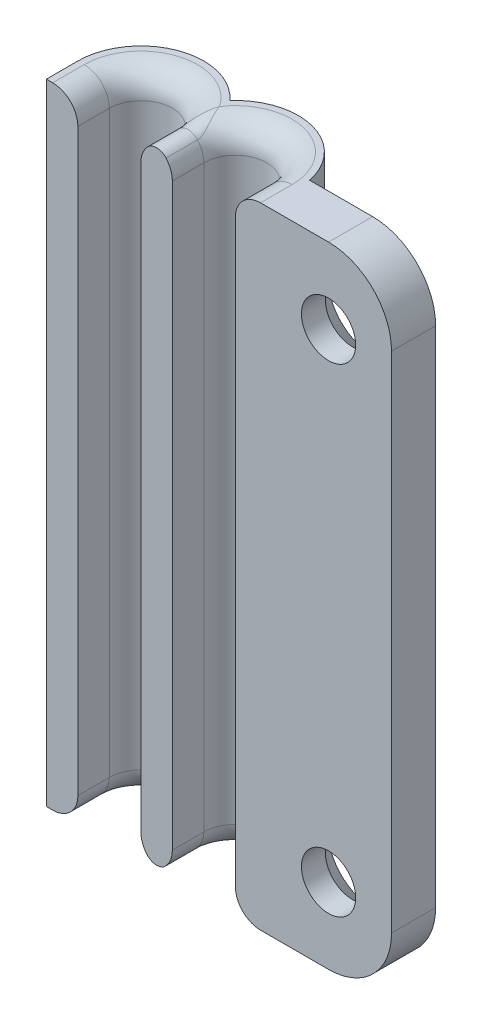
SolidWorks part; units mm, degrees
ref_plane "Top" through (0, 0, 0) normal (0, 0, 1) x (1, 0, 0)
ref_plane "Front" through (0, 0, 0) normal (0, 1, 0) x (1, 0, 0)
ref_plane "Right" through (0, 0, 0) normal (1, 0, 0) x (0, 0, -1)
sketch "Profile Sketch" plane through (0, 0, 0) normal (0, 1, 0) x (1, 0, 0)
  line L1 (0, 0) -> (0, 3.5)
  line L5 (-27.399, 2.5) -> (-27.399, 0)
  line L6 (-19.899, 2.5) -> (-19.899, 0)
  line L7 (-24.899, 2.5) -> (-24.899, 0)
  line L8 (-17.399, 2.5) -> (-17.399, 0)
  line L9 (-12.399, 2.5) -> (-12.399, 0)
  line L10 (-12.399, 0) -> (0, 0)
  line L11 (0, 3.5) -> (-10, 3.5)
  line L13 (-19.899, 0) -> (-17.399, 0)
  line L14 (-24.899, 0) -> (-27.399, 0)
  line L15 (-22.399, 5) -> (-14.899, 5) construction
  arc A0 (-19.899, 2.5) -> (-24.899, 2.5) centre (-22.399, 2.5) ccw
  arc A1 (-12.399, 2.5) -> (-17.399, 2.5) centre (-14.899, 2.5) ccw
  arc A2 (-18.649, 5.8072) -> (-27.399, 2.5) centre (-22.399, 2.5) ccw
  arc A3 (-10, 3.5) -> (-18.649, 5.8072) centre (-14.899, 2.5) ccw
  point P20 (0, 0)
  point P21 (-15, 8.8173)
  point P22 (0, 0)
  dimension "D1" = 3.5
  dimension "D2" = 2.5
  dimension "D4" = 2.5
  dimension "D3" = 10
  dimension "D5" = 5
extrude "Profile Extrude" add sketch "Profile Sketch" along normal blind 50
fillet "Corner Fillets" radius 5 2 edges at (0, 50, -1.75) (0, 0, -1.75)
fillet "Entrance Fillets" radius 2 12 edges at (-22.399, 0, -5) (-14.899, 0, -5) (-14.899, 50, -5) (-22.399, 50, -5) (-24.899, 0, -1.25) (-19.899, 0, -1.25) (-17.399, 0, -1.25) (-12.399, 0, -1.25) (-17.399, 50, -1.25) (-12.399, 50, -1.25) (-24.899, 50, -1.25) (-19.899, 50, -1.25)
fillet "Center Fillets" radius 1 4 edges at (-18.649, 0.146, -1.25) (-18.649, 49.854, -1.25)
hole_wizard "No. 6 Mounting Screws" positions "No. 6 Mounting Screws Position Sketch" profile "No. 6 Mounting Screws Profile Sketch" countersink size "#6" standard "ANSI Inch" end condition through all
sketch "No. 6 Mounting Screws Position Sketch" plane through (0, 0, -3.5) normal (0, 0, -1) x (-1, 0, 0)
  line L0 (0, 25) -> (10, 25) construction
  line L4 (5, 25) -> (5, 0) construction
  line L8 (0, 45) -> (0, 5) construction
  line L10 (5, 0) -> (10, 0) construction
  line L11 (5, 50) -> (10, 50) construction
  line L12 (10, 50) -> (10, 0) construction
  point P0 (5, 44)
  point P2 (5, 6)
  point P24 (0, 0)
  point P25 (0, 0)
  point P26 (9.2002, 20.8342)
  point P27 (0, 0)
  point P28 (1.6699, 20.8753)
  point P31 (0, 0)
  point P34 (0, 0)
  point P35 (0, 0)
  point P38 (5, 9.2061)
  point P41 (0, 0)
  point P42 (0, 0)
  point P43 (0, 0)
  point P44 (0, 0)
  point P45 (0, 0)
  point P46 (0, 0)
  point P47 (7.4558, 23.612)
  point P48 (0, 0)
sketch "No. 6 Mounting Screws Profile Sketch" plane through (-5, 44, -3.5) normal (1, 0, 0) x (0, 1, 0)
  line L0 (0, 0) -> (0, 3.5)
  line L1 (0, 3.5) -> (2.1526, 3.5)
  line L2 (2.1526, 3.5) -> (2.1526, 1.5998)
  line L3 (2.1526, 1.5998) -> (3.5433, 0)
  line L5 (3.5433, 0) -> (0, 0)
  line L6 (-2.1526, 1.5998) -> (-3.5433, 0) construction
  line L11 (0, -6.35) -> (0, 107.95) construction
  dimension "Thru Hole Dia." = 4.3053
  dimension "Thru Hole Depth" = 3.5
  dimension "Near C'Sink Dia." = 7.0866
  dimension "Near C'Sink Angle" = 82
